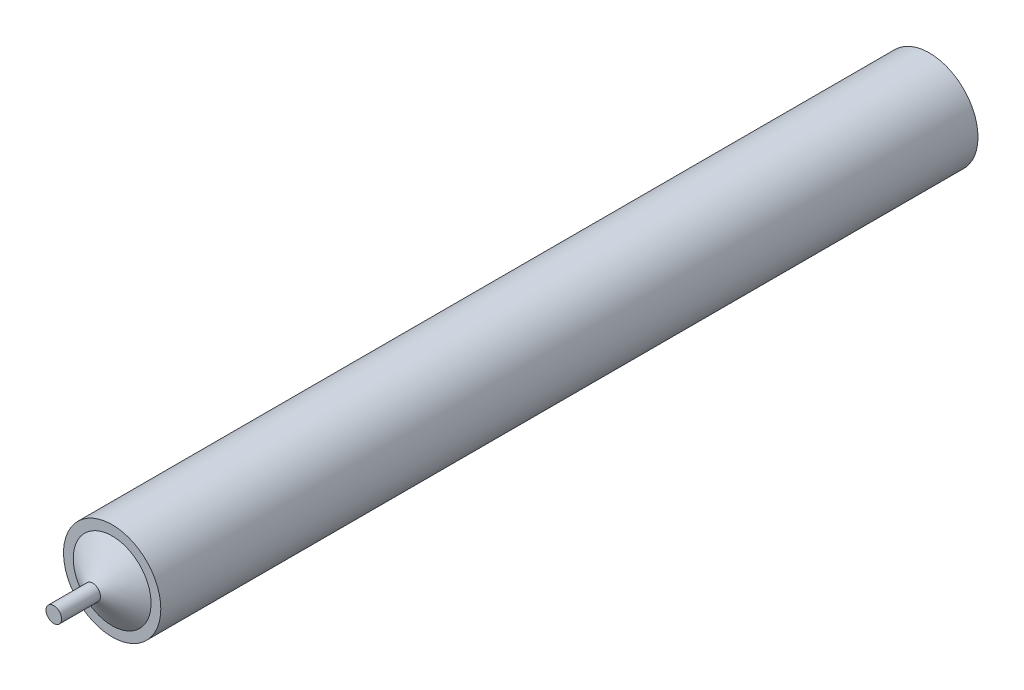
SolidWorks part; units mm, degrees
ref_plane "Piano frontale" through (0, 0, 0) normal (0, 0, 1) x (1, 0, 0)
ref_plane "Piano superiore" through (0, 0, 0) normal (0, 1, 0) x (1, 0, 0)
ref_plane "Piano destro" through (0, 0, 0) normal (1, 0, 0) x (0, 0, -1)
sketch "Schizzo1" plane through (0, 0, 0) normal (0, 0, 1) x (1, 0, 0)
  circle A0 centre (0, 0) radius 25
  dimension "D1" = 50
extrude "Estrusione-Estrusione1" add sketch "Schizzo1" along normal blind 420 contours A0
sketch "Schizzo4" plane through (0, 0, 420) normal (0, 0, 1) x (1, 0, 0)
  circle A0 centre (0, 0) radius 20
  dimension "D1" = 40
ref_plane "Piano1" through (0, 0, 430) normal (0, 0, 1) x (1, 0, 0)
sketch "Schizzo5" plane through (0, 0, 430) normal (0, 0, 1) x (1, 0, 0)
  circle A0 centre (0, 0) radius 4
  dimension "D1" = 8
loft "Loft2" add profiles "Schizzo5", "Schizzo4" connector at (3.9258, -0.7668, 430) connector at (19.9728, -1.0425, 420)
sketch "Schizzo9" plane through (0, 0, 430) normal (0, 0, 1) x (1, 0, 0)
  circle A0 centre (0, 0) radius 4
extrude "Estrusione-Estrusione2" add sketch "Schizzo9" along normal blind 20
ref_plane "Piano2" through (0, 0, -10) normal (0, 0, -1) x (-1, 0, 0)
sketch "Schizzo10" plane through (0, 0, -10) normal (0, 0, -1) x (-1, 0, 0)
  circle A0 centre (0, 0) radius 2.5
  dimension "D1" = 5
sketch "Schizzo11" plane through (0, 0, 0) normal (0, 0, -1) x (-1, 0, 0)
  circle A0 centre (0, 0) radius 20
  dimension "D1" = 40
loft "Loft3" add profiles "Schizzo11", "Schizzo10" connector at (-8.0121, 18.325, 0) connector at (-0.3554, 2.4746, -10)
sketch "Schizzo12" plane through (0, 0, -10) normal (0, 0, -1) x (-1, 0, 0)
  circle A0 centre (0, 0) radius 2.5
extrude "Taglio-Estrusione2" cut sketch "Schizzo12" against normal blind 25
